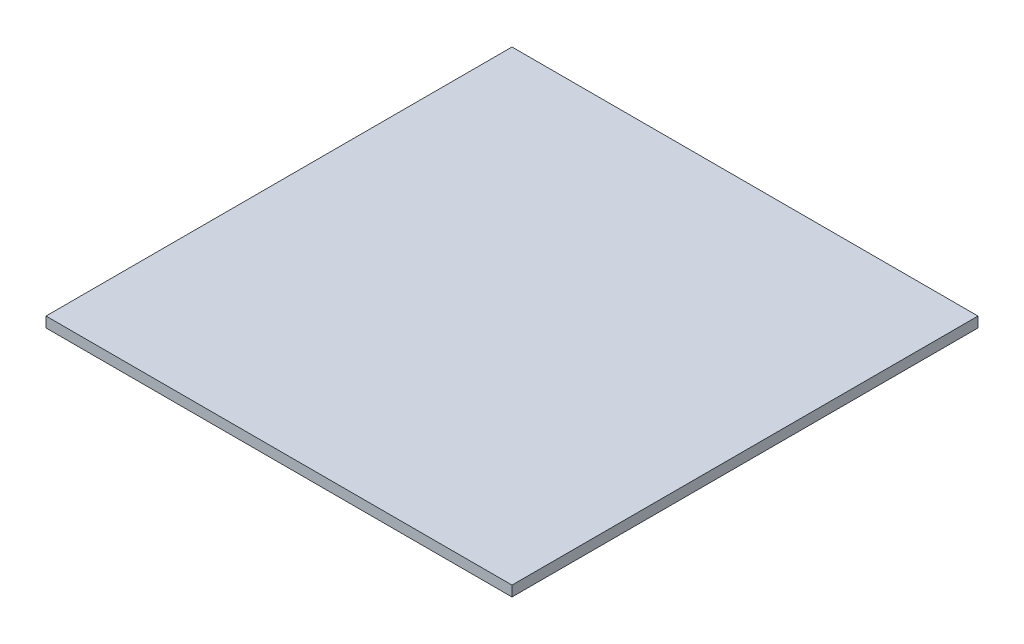
SolidWorks part; units mm, degrees
ref_plane "Ebene vorne" through (0, 0, 0) normal (0, 0, 1) x (1, 0, 0)
ref_plane "Ebene oben" through (0, 0, 0) normal (0, 1, 0) x (1, 0, 0)
ref_plane "Ebene rechts" through (0, 0, 0) normal (1, 0, 0) x (0, 0, -1)
sketch "Skizze1" plane through (0, 0, 0) normal (0, 1, 0) x (1, 0, 0)
  line L1 (-45, 45) -> (45, 45)
  line L2 (-45, 45) -> (-45, -45)
  line L3 (-45, -45) -> (45, -45)
  line L4 (45, 45) -> (45, -45)
  line L5 (-45, 45) -> (45, -45) construction
  line L6 (-45, -45) -> (45, 45) construction
  point P0 (0, 0)
  dimension "D1" = 90
  dimension "D2" = 90
extrude "Aufsatz-Linear austragen1" add sketch "Skizze1" along normal blind 2
